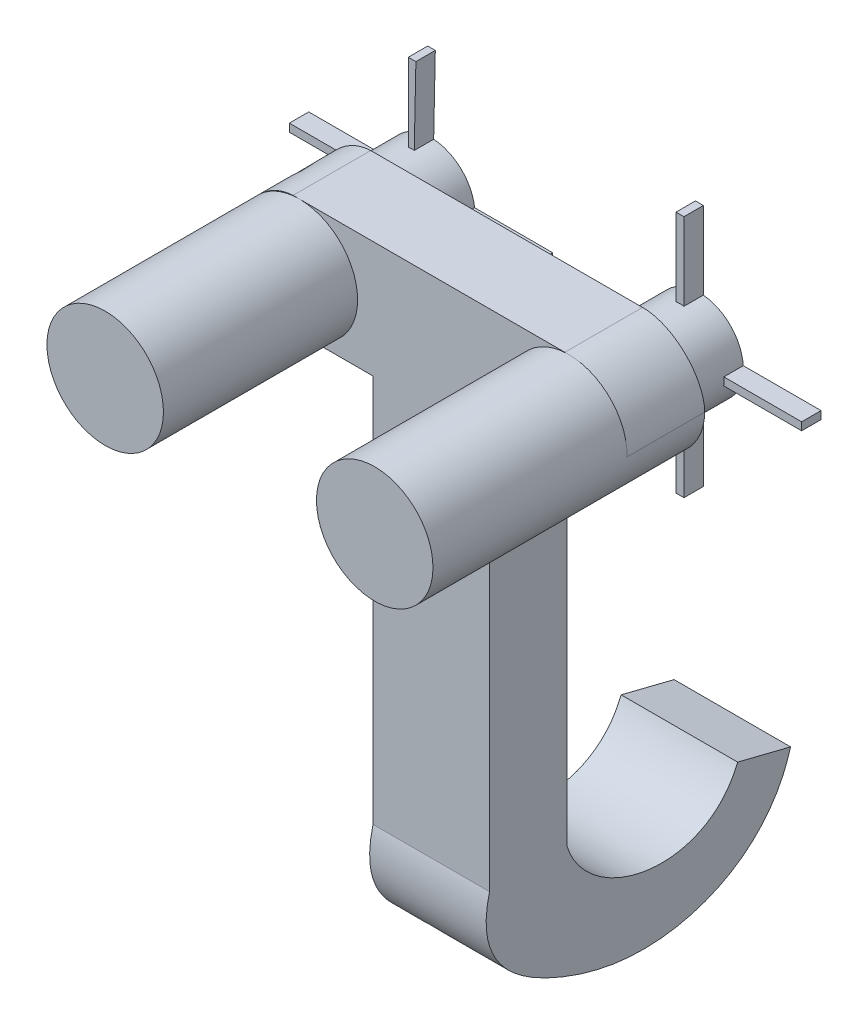
SolidWorks part; units mm, degrees
ref_plane "前基準面" through (0, 0, 0) normal (0, 0, 1) x (1, 0, 0)
ref_plane "上基準面" through (0, 0, 0) normal (0, 1, 0) x (1, 0, 0)
ref_plane "右基準面" through (0, 0, 0) normal (1, 0, 0) x (0, 0, -1)
sketch "草圖3" plane through (0, 0, 0) normal (0, 0, 1) x (1, 0, 0)
  line L0 (-30.2049, 52.9888) -> (-30.2049, -20.18) construction
  circle A0 centre (-33.6751, 21.6888) radius 1.5
  circle A1 centre (-26.7347, 21.6888) radius 1.5
extrude "填料-伸長1" add sketch "草圖3" along normal blind 5
sketch "草圖4" plane through (0, 0, 0) normal (0, 0, -1) x (-1, 0, 0)
  line L0 (25.2347, 21.6888) -> (28.2347, 21.6888) construction
  line L1 (28.2347, 21.6888) -> (32.1751, 21.6888) construction
  line L2 (32.1751, 21.6888) -> (35.1751, 21.6888) construction
  line L4 (33.7737, 20.1888) -> (26.6285, 20.1888)
  line L5 (35.1751, 21.6477) -> (35.1751, 21.6721)
  line L6 (33.8372, 23.1888) -> (26.8382, 23.1888)
  line L7 (25.2347, 21.6069) -> (25.2347, 21.6894)
  line L8 (34.4772, 20.3994) -> (26.042, 22.9451) construction
  line L9 (34.4669, 22.975) -> (25.9414, 20.4021) construction
  circle A0 centre (26.7347, 21.6888) radius 1.5 construction
  circle A1 centre (33.6751, 21.6888) radius 1.5 construction
  spline S0 degree 3 poles (33.8372, 23.1888) (34.5625, 23.155) (35.8009, 21.6707) (34.5359, 20.1659) (33.7737, 20.1888) knots 0 0 0 0 0.492243 1 1 1 1
  spline S1 degree 3 poles (26.6285, 20.1888) (25.9176, 20.1787) (24.4851, 21.7098) (26.0569, 23.204) (26.8382, 23.1888) knots 0 0 0 0 0.46906 1 1 1 1
  point P5 (30.2049, 21.6888)
  circle M1 centre (26.7347, 21.6888) radius 1.5
extrude "填料-伸長2" add sketch "草圖4" along normal blind 2 contours S1 L4 S0 L6 M1 | S1 M1 region at (-31.3861, 21.6882, 0) region at (-26.7499, 21.6732, 0)
ref_plane "平面1" through (0, 10.1888, 0) normal (0, -1, 0) x (-1, 0, 0)
sketch "草圖5" plane through (0, 10.1888, 0) normal (0, -1, 0) x (-1, 0, 0)
  line L0 (30.2049, 0) -> (30.2049, 2) construction
  line L1 (33.6751, 0) -> (26.7347, 0) construction
  line L2 (33.7737, 2) -> (26.7347, 2) construction
  line L4 (31.6317, 0) -> (28.7782, 0)
  line L5 (31.6317, 0) -> (31.6317, 2)
  line L6 (31.6317, 2) -> (28.7782, 2)
  line L7 (28.7782, 0) -> (28.7782, 2)
  line L8 (31.6317, 0) -> (28.7782, 2) construction
  line L9 (31.6317, 2) -> (28.7782, 0) construction
  point P6 (30.2049, 1)
extrude "填料-伸長3" add sketch "草圖5" against normal blind 10
sketch "草圖8" plane through (-28.7782, 0, 0) normal (1, 0, 0) x (0, 0, -1)
  line L0 (7.7533, 9.5423) -> (6.3898, 9.8841)
  line L5 (0, 10.1888) -> (2, 10.1888)
  line L6 (2, 10.1888) -> (2, 20.1888)
  line L7 (2, 20.1888) -> (0, 20.1888)
  line L8 (0, 20.1888) -> (0, 10.1888)
  line L10 (2, 10.1888) -> (2, 20.1888)
  line L11 (2, 20.1888) -> (0, 20.1888)
  line L12 (0, 20.1888) -> (0, 10.1888)
  spline S0 degree 3 poles (2, 10.1888) (2.5584, 8.4634) (5.5808, 7.861) (6.3898, 9.8841) knots 0 0 0 0 1 1 1 1
  spline S1 degree 3 poles (0, 10.1888) (-0.3986, 8.6485) (1.2455, 7.424) (4.7066, 6.5307) (7.2182, 7.6434) (7.7533, 9.5423) knots 0 0 0 0 0.333348 0.52695 1 1 1 1
  dimension "D1" = 0
extrude "填料-伸長4" add sketch "草圖8" against normal blind 3
sketch "草圖10" plane through (0, 0, -2) normal (0, 0, -1) x (-1, 0, 0)
  circle A0 centre (26.882, 21.6123) radius 1.1409
  circle A1 centre (33.7933, 21.6123) radius 1.1409
extrude "填料-伸長5" add sketch "草圖10" along normal blind 1.5
sketch "草圖11" plane through (0, 0, -3.5) normal (0, 0, -1) x (-1, 0, 0)
  line L2 (25.7436, 21.6874) -> (23.7403, 21.6874)
  line L3 (23.7403, 21.6874) -> (23.7403, 21.4858)
  line L4 (23.7403, 21.4858) -> (25.7481, 21.4858)
  line L5 (30.0237, 21.6874) -> (30.0237, 21.4858)
  line L6 (30.0237, 21.4858) -> (28.0159, 21.4858)
  line L7 (28.0205, 21.6874) -> (30.0237, 21.6874)
  line L8 (26.9753, 20.4752) -> (26.9753, 18.4786)
  line L9 (26.9753, 18.4786) -> (26.7713, 18.4786)
  line L10 (26.7713, 18.4786) -> (26.7713, 20.4768)
  line L11 (26.9753, 24.746) -> (26.7713, 24.746)
  line L12 (26.7713, 24.746) -> (26.7713, 22.7478)
  line L13 (26.9753, 22.7494) -> (26.9753, 24.746)
  circle A0 centre (26.882, 21.6123) radius 1.1409 construction
  spline S0 degree 1 poles (28.0159, 21.4858) (28.0205, 21.6874) knots 0 0 1 1
  spline S1 degree 1 poles (26.9753, 20.4752) (26.7713, 20.4768) knots 0 0 1 1
  spline S2 degree 1 poles (25.7481, 21.4858) (25.7436, 21.6874) knots 0 0 1 1
  spline S3 degree 1 poles (26.9753, 22.7494) (26.7713, 22.7478) knots 0 0 1 1
extrude "填料-伸長7" add sketch "草圖11" against normal blind 0.5
sketch "草圖13" plane through (0, 0, -3.5) normal (0, 0, -1) x (-1, 0, 0)
  line L0 (33.7933, 20.4714) -> (33.7933, 22.7532) construction
  line L1 (33.8703, 20.474) -> (33.8703, 18.4714)
  line L2 (33.8703, 18.4714) -> (33.6742, 18.4714)
  line L3 (33.6742, 18.4714) -> (33.7164, 20.474)
  line L4 (33.8703, 20.474) -> (33.7164, 20.474)
  line L5 (34.9342, 21.6123) -> (32.6524, 21.6123) construction
  line L6 (33.8703, 22.7506) -> (33.7164, 22.7506)
  line L7 (33.8703, 24.7532) -> (33.6742, 24.7532)
  line L8 (33.6742, 24.7532) -> (33.7164, 22.7506)
  line L9 (33.8703, 22.7506) -> (33.8703, 24.7532)
  line L10 (32.6542, 21.5482) -> (30.6531, 21.5482)
  line L11 (30.6531, 21.5482) -> (30.6531, 21.752)
  line L12 (30.6531, 21.752) -> (32.661, 21.752)
  line L13 (32.661, 21.752) -> (32.6542, 21.5482)
  line L14 (36.9336, 21.5482) -> (36.9336, 21.752)
  line L15 (34.9257, 21.752) -> (34.9324, 21.5482)
  line L16 (36.9336, 21.752) -> (34.9257, 21.752)
  line L17 (34.9324, 21.5482) -> (36.9336, 21.5482)
  circle A0 centre (33.7933, 21.6123) radius 1.1409 construction
extrude "填料-伸長8" add sketch "草圖13" against normal blind 0.5
